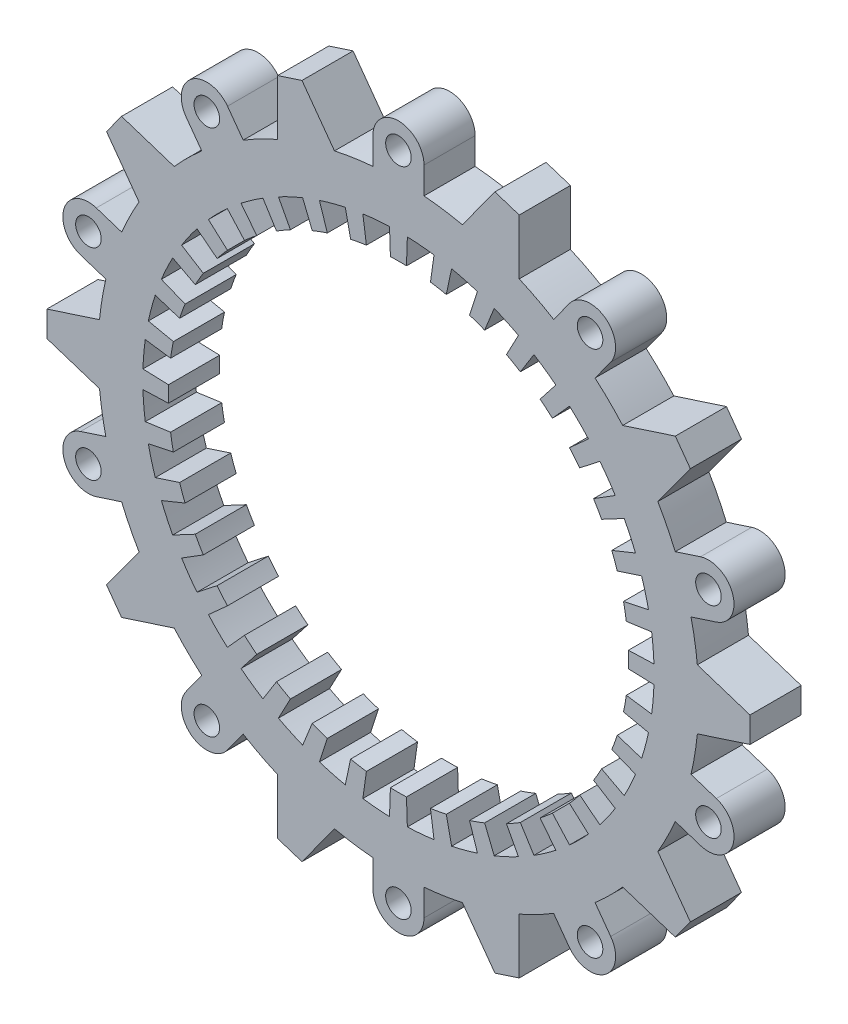
SolidWorks part; units mm, degrees
ref_plane "Front Plane" through (0, 0, 0) normal (0, 0, 1) x (1, 0, 0)
ref_plane "Top Plane" through (0, 0, 0) normal (0, 1, 0) x (1, 0, 0)
ref_plane "Right Plane" through (0, 0, 0) normal (1, 0, 0) x (0, 0, -1)
sketch "Sketch1" plane through (0, 0, 0) normal (0, 0, 1) x (1, 0, 0)
  circle A0 centre (0, 0) radius 57.5 construction
  circle A1 centre (0, 0) radius 40 construction
  circle A2 centre (0, 0) radius 27.5 construction
  circle A3 centre (0, 0) radius 20 construction
  circle A4 centre (0, 0) radius 12.5 construction
  circle A5 centre (0, 0) radius 9.5 construction
  dimension "D1" = 115
  dimension "D2" = 80
  dimension "D3" = 55
  dimension "D4" = 40
  dimension "D5" = 25
  dimension "D6" = 19
sketch "Sketch3" plane through (0, 0, 0) normal (0, 0, 1) x (1, 0, 0)
  line L0 (0, 0) -> (0, 20) construction
  line L1 (0, 0) -> (-0.698, 19.9878) construction
  line L2 (0, 0) -> (0.698, 19.9878) construction
  line L3 (-0.6282, 17.989) -> (-0.698, 19.9878)
  line L4 (0.6282, 17.989) -> (0.698, 19.9878)
  line L5 (-2, 25.5) -> (-2, 23.4147)
  line L6 (2, 25.5) -> (2, 23.4147)
  line L7 (0, 0) -> (0, -27.5) construction
  line L11 (0, 0) -> (-8.498, -26.1541) construction
  line L12 (-9.449, -25.845) -> (-7.5469, -26.4631)
  line L13 (-9.449, -25.845) -> (-9.449, -21.5166)
  line L14 (-7.5469, -26.4631) -> (-5.0027, -22.9613)
  line L15 (-9.449, -21.5166) -> (-5.0027, -22.9613) construction
  circle A0 centre (0, 0) radius 23.5
  circle A1 centre (0, 0) radius 20
  arc A3 (-0.6282, 17.989) -> (0.6282, 17.989) centre (0, 0) cw
  circle A4 centre (0, 0) radius 18
  circle A5 centre (0, 25.5) radius 2
  circle A6 centre (0, 25.5) radius 1
  circle A7 centre (0, 0) radius 27.5 construction
  point P22 (0, 27.5)
  dimension "D1" = 47
  dimension "D2" = 40
  dimension "D5" = 4
  dimension "D7" = 2
  dimension "D3" = 2
  dimension "D11" = 18
  dimension "D12" = 27.5
  dimension "D13" = 2
  dimension "D14" = 108
  dimension "D15" = 4.6751
  dimension "D6" = 27.5
extrude "Boss-Extrude2" add sketch "Sketch3" along normal blind 4 contours A0 A1 region at (-0.9726, 22.8146, 0)
extrude "Boss-Extrude3" add sketch "Sketch3<4>" along normal blind 4 contours L3 A3 L4 A1 region at (0, 19.0137, 0)
sketch "Sketch3<4>" plane through (0, 0, 0) normal (0, 0, 1) x (1, 0, 0) same geometry as "Sketch3"
ref_axis "Axis1" through (0, 0, 0) along (0, 0, 1)
pattern_circular "CirPattern1" count 36 over 360 about axis through (0, 0, 0) along (0, 0, 1) of "Boss-Extrude3"
extrude "Boss-Extrude4" add sketch "Sketch3<5>" along normal blind 4 contours A5 A6 | A5 L5 A0 | A5 A0 L6 region at (-1.55, 23.9174, 0) region at (0, 27.4434, 0) region at (1.55, 23.9174, 0)
sketch "Sketch3<5>" plane through (0, 0, 0) normal (0, 0, 1) x (1, 0, 0) same geometry as "Sketch3"
pattern_circular "CirPattern2" count 10 over 360 about axis through (0, 0, 0) along (0, 0, 1) of "Boss-Extrude4"
extrude "Boss-Extrude5" add sketch "Sketch3<6>" along normal blind 4 contours A0 L13 L12 L14 region at (-7.7915, -23.9799, 0)
sketch "Sketch3<6>" plane through (0, 0, 0) normal (0, 0, 1) x (1, 0, 0) same geometry as "Sketch3"
pattern_circular "CirPattern3" count 10 over 360 about axis through (0, 0, 0) along (0, 0, 1) of "Boss-Extrude5"
equation "\"tyre_ID\"= 115mm"
equation "\"disc_OD\" = 80mm"
equation "\"discbell_OD\" = 55mm"
equation "\"hub_OD\" = 40"
equation "\"bearing_ID\" = 25mm"
equation "\"shaft_OD\"= 19mm"
equation "\"D1@Sketch1\"=\"tyre_ID\""
equation "\"D2@Sketch1\"=\"disc_OD\""
equation "\"D3@Sketch1\"=\"discbell_OD\""
equation "\"D4@Sketch1\"=\"hub_OD\""
equation "\"D5@Sketch1\"=\"bearing_ID\""
equation "\"D6@Sketch1\"=\"shaft_OD\""
equation "\"D1@Sketch3\"=\"discbell_OD\"-8"
equation "\"D2@Sketch3\"=\"hub_OD\""
equation "\"D12@Sketch3\"=\"discbell_OD\"/2"
equation "\"D6@Sketch3\"=\"discbell_OD\"/2"
